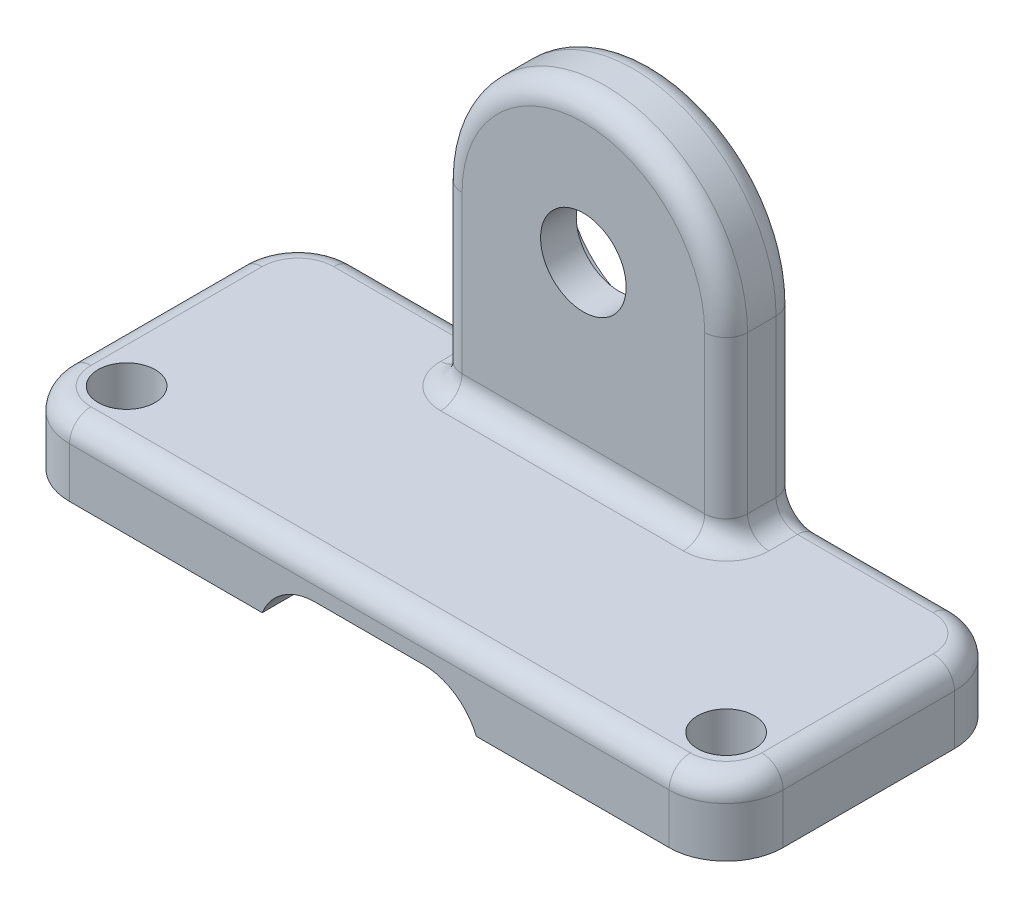
SolidWorks part; units mm, degrees
material "Латунь"
ref_plane "Спереди" through (0, 0, 0) normal (0, 0, 1) x (1, 0, 0)
ref_plane "Сверху" through (0, 0, 0) normal (0, 1, 0) x (1, 0, 0)
ref_plane "Справа" through (0, 0, 0) normal (1, 0, 0) x (0, 0, -1)
sketch "Эскиз3" plane through (0, 0, 0) normal (0, 1, 0) x (1, 0, 0)
  line L0 (-50, 20) -> (50, -20) construction
  line L1 (-50, 20) -> (50, 20)
  line L2 (-50, 20) -> (-50, -20)
  line L3 (-50, -20) -> (50, -20)
  line L4 (50, 20) -> (50, -20)
  line L5 (50, 20) -> (-50, -20) construction
  dimension "D1" = 40
  dimension "D2" = 100
extrude "Бобышка-Вытянуть1" add sketch "Эскиз3" along normal blind 10 contours L1 L4 L3 L2
sketch "Эскиз4" plane through (0, 0, -20) normal (0, 0, -1) x (-1, 0, 0)
  line L0 (-20, 0) -> (-20, 35)
  line L1 (50, 0) -> (-50, 0) construction
  line L2 (20, 35) -> (20, 0)
  line L3 (20, 0) -> (-20, 0)
  line L4 (-50, 10) -> (-50, 0) construction
  arc A0 (-20, 35) -> (20, 35) centre (0, 35) cw
  point P4 (0, 0)
  point P8 (0, 0)
  point P9 (18.3016, 46.3072)
  point P10 (20.8227, 46.2605)
  point P11 (-25.3047, 45.0296)
  point P12 (-25.3981, 45.0296)
  point P13 (-25.5848, 47.1772)
  dimension "D1" = 50
  dimension "D3" = 20
  dimension "D2" = 35
extrude "Бобышка-Вытянуть3" add sketch "Эскиз4" against normal blind 10 contours A0 L2 L3 L0
sketch "Эскиз6" plane through (0, 0, -20) normal (0, 0, -1) x (-1, 0, 0)
  circle A0 centre (0, 35) radius 12.5
  dimension "D1" = 25
extrude "Вырез-Вытянуть1" cut sketch "Эскиз6" against normal blind 5 contours A0
sketch "Эскиз8" plane through (0, 0, -15) normal (0, 0, -1) x (-1, 0, 0)
  circle A0 centre (0, 35) radius 6
extrude "Вырез-Вытянуть2" cut sketch "Эскиз8" against normal blind 5
sketch "Эскиз9" plane through (0, 0, -20) normal (0, 0, -1) x (-1, 0, 0)
  line L0 (50, 0) -> (-50, 0) construction
  line L1 (-15, 0) -> (15, 0)
  line L2 (-15, 0) -> (-15, 5)
  line L3 (-15, 5) -> (15, 5)
  line L4 (15, 0) -> (15, 5)
  line L5 (-50, 10) -> (-50, 0) construction
  dimension "D1" = 35
  dimension "D2" = 30
  dimension "D3" = 5
extrude "Вырез-Вытянуть4" cut sketch "Эскиз9" against normal through all
fillet "Скругление1" radius 8 6 edges at (-15, 5, 0) (15, 5, 0) (-50, 5, 20) (-50, 5, -20) (50, 5, 20) (50, 5, -20)
sketch "Эскиз12" plane through (0, 10, 0) normal (0, 1, 0) x (1, 0, 0)
  line L0 (0, 41.412) -> (0, -41.412) construction
  line L1 (-42, -20) -> (42, -20) construction
  circle A0 centre (-42, -12) radius 4
  circle A1 centre (42, -12) radius 4
  point P4 (0, 0)
  dimension "D1" = 84
  dimension "D2" = 8
  dimension "D3" = 8
extrude "Вырез-Вытянуть6" cut sketch "Эскиз12" against normal through all
fillet "Скругление2" radius 3 18 edges at (0, 55, -20) (-20, 22.5, -20) (20, 22.5, -20) (-20, 22.5, -10) (0, 55, -10) (-31, 10, -20) (-47.6569, 10, -17.6569) (31, 10, -20) (47.6569, 10, -17.6569) (50, 10, 0) (47.6569, 10, 17.6569) (0, 10, 20) (-47.6569, 10, 17.6569) (20, 22.5, -10) (0, 10, -10) (20, 10, -15) (-20, 10, -15) (-50, 10, 0)
